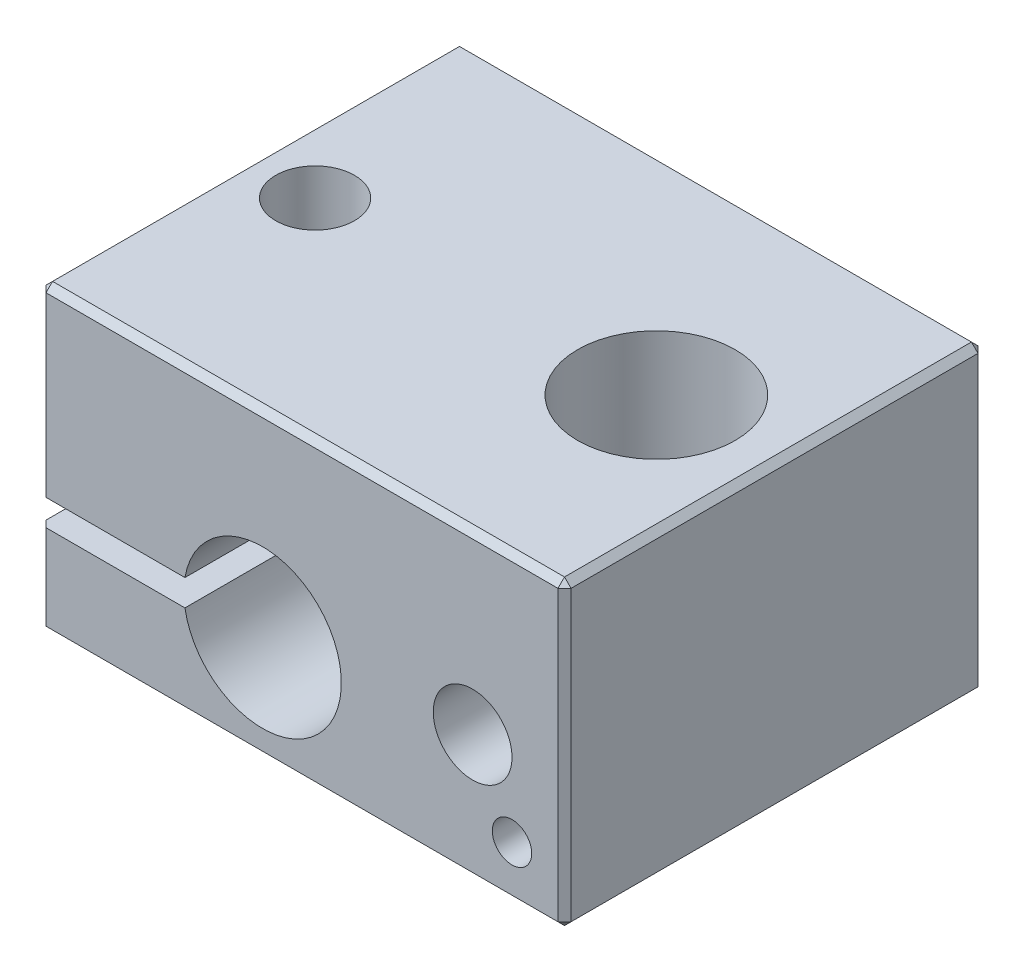
SolidWorks part; units mm, degrees
material "1060 Alloy"
ref_plane "Front Plane" through (0, 0, 0) normal (0, 0, 1) x (1, 0, 0)
ref_plane "Top Plane" through (0, 0, 0) normal (0, 1, 0) x (1, 0, 0)
ref_plane "Right Plane" through (0, 0, 0) normal (1, 0, 0) x (0, 0, -1)
ref_plane "Plane1" through (0, 0, 0) normal (0, -1, 0) x (1, 0, 0)
sketch "Sketch1" plane through (0, 0, 0) normal (0, -1, 0) x (1, 0, 0)
  line L0 (10, -8) -> (10, 8)
  line L1 (10, 8) -> (-10, 8)
  line L2 (-10, 8) -> (-10, -8)
  line L3 (-10, -8) -> (10, -8)
extrude "Boss-Extrude1" add sketch "Sketch1" against normal blind 11.5
sketch "Sketch2" plane through (0, 0, -8) normal (0, 0, -1) x (-1, 0, 0)
  line L0 (10, 3.5) -> (10, 4.5)
  line L1 (10, 4.5) -> (4.458, 4.5)
  line L2 (4.458, 3.5) -> (10, 3.5)
  arc A0 (4.458, 4.5) -> (4.458, 3.5) centre (1.5, 4) cw
extrude "Cut-Extrude1" cut sketch "Sketch2" against normal through all
ref_plane "Plane2" through (0, 4, 0) normal (0, 1, 0) x (1, 0, 0)
sketch "Sketch3" plane through (0, 4, 0) normal (0, 1, 0) x (1, 0, 0)
  line L0 (1.5, 8) -> (-1.5, 8)
  line L1 (-1.5, 8) -> (-1.5, -8)
  line L2 (-1.5, -8) -> (1.5, -8)
  line L3 (1.5, -8) -> (1.5, 8)
  line L4 (-1.5, 8) -> (-1.5, -8) construction
revolve "Cut-Revolve1" cut sketch "Sketch3" angle 360 about L4 reverse direction yes
hole_wizard "Ø3.0 (3) Diameter Hole1" positions "Sketch5" profile "Sketch4" hole size "Ø3.0" standard "ANSI Metric"
sketch "Sketch5" plane through (0, 4.5, 0) normal (0, -1, 0) x (-1, 0, 0)
  point P0 (7.5, 0)
sketch "Sketch4" plane through (-7.5, 4.5, 0) normal (1, 0, 0) x (0, 0, -1)
  line L0 (0, 0) -> (0, 7)
  line L1 (0, 7) -> (1.5, 7)
  line L2 (1.5, 7) -> (1.5, 0)
  line L5 (1.5, 0) -> (0, 0)
  line L11 (0, -6.35) -> (0, 107.95) construction
  dimension "Thru Hole Dia." = 3
  dimension "Thru Hole Depth" = 7
hole_wizard "Ø6.0 (6) Diameter Hole1" positions "Sketch7" profile "Sketch6" hole size "Ø6.0" standard "ANSI Metric"
sketch "Sketch7" plane through (0, 0, 0) normal (0, -1, 0) x (-1, 0, 0)
  point P0 (-5.5, 0)
sketch "Sketch6" plane through (5.5, 0, 0) normal (1, 0, 0) x (0, 0, -1)
  line L0 (0, 0) -> (0, 11.5)
  line L1 (0, 11.5) -> (3, 11.5)
  line L2 (3, 11.5) -> (3, 0)
  line L5 (3, 0) -> (0, 0)
  line L11 (0, -6.35) -> (0, 107.95) construction
  dimension "Thru Hole Dia." = 6
  dimension "Thru Hole Depth" = 11.5
hole_wizard "Ø3.0 (3) Diameter Hole2" positions "Sketch9" profile "Sketch8" hole size "Ø3.0" standard "ANSI Metric"
sketch "Sketch9" plane through (0, 3.5, 0) normal (0, 1, 0) x (1, 0, 0)
  point P0 (-7.5, 0)
sketch "Sketch8" plane through (-7.5, 3.5, 0) normal (1, 0, 0) x (0, 0, 1)
  line L0 (0, 0) -> (0, 3.5)
  line L1 (0, 3.5) -> (1.5, 3.5)
  line L2 (1.5, 3.5) -> (1.5, 0)
  line L5 (1.5, 0) -> (0, 0)
  line L11 (0, -6.35) -> (0, 107.95) construction
  dimension "Thru Hole Dia." = 3
  dimension "Thru Hole Depth" = 3.5
hole_wizard "Ø3.0 (3) Diameter Hole3" positions "Sketch11" profile "Sketch10" hole size "Ø3.0" standard "ANSI Metric"
sketch "Sketch11" plane through (0, 0, 8) normal (0, 0, 1) x (1, 0, 0)
  point P0 (6.5, 4.8)
sketch "Sketch10" plane through (6.5, 4.8, 8) normal (1, 0, 0) x (0, -1, 0)
  line L0 (0, 0) -> (0, 3.5)
  line L1 (0, 3.5) -> (1.5, 3.5)
  line L2 (1.5, 3.5) -> (1.5, 0)
  line L5 (1.5, 0) -> (0, 0)
  line L10 (0, 3.5) -> (-1.5, 3.5) construction
  line L11 (0, -6.35) -> (0, 107.95) construction
  dimension "Hole Dia." = 3
  dimension "Hole Depth" = 3.5
  dimension "Drill Angle" = 180
hole_wizard "Ø1.5 (1.5) Diameter Hole1" positions "Sketch13" profile "Sketch12" hole size "Ø1.5" standard "ANSI Metric"
sketch "Sketch13" plane through (0, 0, 8) normal (0, 0, 1) x (1, 0, 0)
  point P0 (8, 2)
sketch "Sketch12" plane through (8, 2, 8) normal (1, 0, 0) x (0, -1, 0)
  line L0 (0, 0) -> (0, 4.5)
  line L1 (0, 4.5) -> (0.75, 4.5)
  line L2 (0.75, 4.5) -> (0.75, 0)
  line L5 (0.75, 0) -> (0, 0)
  line L10 (0, 4.5) -> (-0.75, 4.5) construction
  line L11 (0, -6.35) -> (0, 107.95) construction
  dimension "Hole Dia." = 1.5
  dimension "Hole Depth" = 4.5
  dimension "Drill Angle" = 180
chamfer "Chamfer1" distance 0.25 angle 45 14 edges at (-10, 1.75, -8) (-10, 0, 0) (-10, 1.75, 8) (0, 0, -8) (0, 0, 8) (10, 0, 0) (-10, 8, -8) (-10, 11.5, 0) (-10, 8, 8) (10, 5.75, -8) (10, 5.75, 8) (0, 11.5, -8) (0, 11.5, 8) (10, 11.5, 0)
